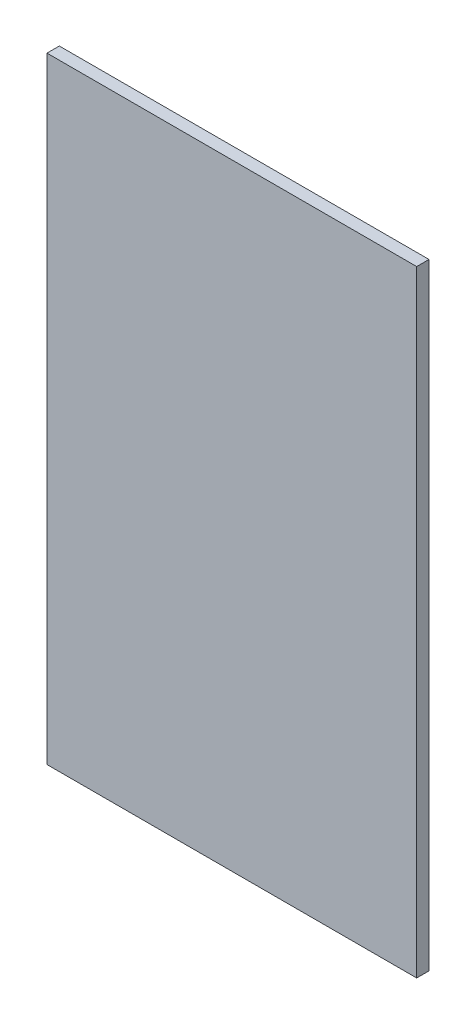
SolidWorks part; units mm, degrees
ref_plane "Front" through (0, 0, 0) normal (0, 0, 1) x (1, 0, 0)
ref_plane "Top" through (0, 0, 0) normal (0, 1, 0) x (1, 0, 0)
ref_plane "Right" through (0, 0, 0) normal (1, 0, 0) x (0, 0, -1)
sketch "Esquisse1" plane through (0, 0, 0) normal (0, 0, 1) x (1, 0, 0)
  line L1 (0, 0) -> (900, 0)
  line L2 (0, 0) -> (0, 1500)
  line L3 (0, 1500) -> (900, 1500)
  line L4 (900, 0) -> (900, 1500)
  dimension "D1" = 900
  dimension "D2" = 1500
extrude "Boss.-Extru.1" add sketch "Esquisse1" along normal blind 30
